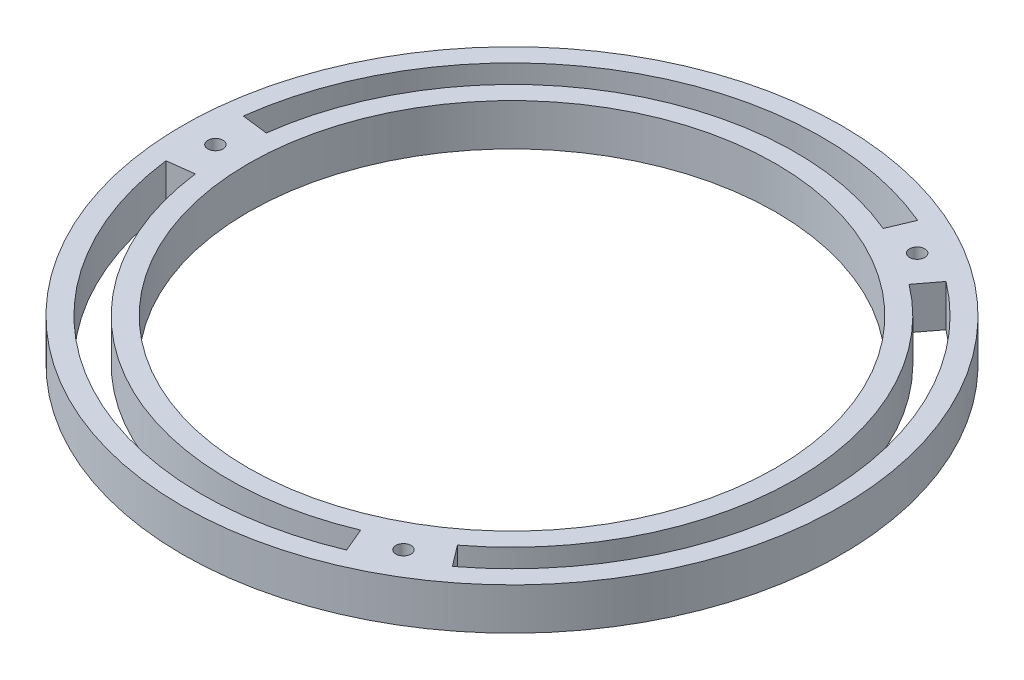
SolidWorks part; units mm, degrees
ref_plane "Front Plane" through (0, 0, 0) normal (0, 0, 1) x (1, 0, 0)
ref_plane "Top Plane" through (0, 0, 0) normal (0, 1, 0) x (1, 0, 0)
ref_plane "Right Plane" through (0, 0, 0) normal (1, 0, 0) x (0, 0, -1)
sketch "Sketch1" plane through (0, 0, 0) normal (0, 1, 0) x (1, 0, 0)
  line L0 (-50, 0) -> (50, 0) construction
  line L1 (-25, 43.3013) -> (25, -43.3013) construction
  line L2 (-25, -43.3013) -> (25, 43.3013) construction
  line L3 (30.2166, 39.8366) -> (24.1733, 31.8693)
  line L4 (19.3913, 46.0866) -> (15.513, 36.8693)
  line L5 (30.2166, -39.8366) -> (24.1733, -31.8693)
  line L6 (19.3913, -46.0866) -> (15.513, -36.8693)
  line L7 (-49.6078, 6.25) -> (-39.6863, 5)
  line L8 (-49.6078, -6.25) -> (-39.6863, -5)
  line L9 (0, 0) -> (15.513, 36.8693) construction
  line L10 (0, 0) -> (24.1733, 31.8693) construction
  line L11 (0, 0) -> (24.1733, -31.8693) construction
  line L12 (0, 0) -> (15.513, -36.8693) construction
  line L13 (0, 0) -> (-39.6863, 5) construction
  line L14 (-39.6863, -5) -> (0, 0) construction
  circle A0 centre (0, 0) radius 50
  circle A1 centre (0, 0) radius 47
  circle A2 centre (0, 0) radius 43
  circle A3 centre (0, 0) radius 40
  point P10 (0, 0)
  point P14 (0, 0)
  point P17 (0, 0)
  dimension "D1" = 100
  dimension "D2" = 3
  dimension "D5" = 60
  dimension "D6" = 60
  dimension "D7" = 5
  dimension "D8" = 5
  dimension "D9" = 5
  dimension "D10" = 5
  dimension "D11" = 5
  dimension "D12" = 5
  dimension "D3" = 4
  dimension "D4" = 3
extrude "Boss-Extrude1" add sketch "Sketch1" along normal blind 6.35 contours A1 L5 A0 L3 | A3 L5 A2 L3 | A3 L6 A2 L5 | A2 L6 A1 L5 | A1 L6 A0 L5 | A1 L8 A0 L6 | A3 L8 A2 L6 | A3 L7 A2 L8 | A2 L7 A1 L8 | A1 L7 A0 L8 | A1 L4 A0 L7 | A3 L4 A2 L7 | A3 L3 A2 L4 | A2 L3 A1 L4 | A1 L3 A0 L4 region at (44.0425, 0, -21.8721) region at (24.1943, 0, -41.9057) region at (22.4559, 0, -38.8948) region at (18.0546, 0, -45.0217) region at (37.876, 0, -18.8097) region at (20.7047, 0, -35.8617) region at (24.1943, 0, 41.9057) region at (-48.3886, 0, 0) region at (15.4453, 0, -38.5252) region at (22.4559, 0, 38.8948) region at (-44.9118, 0, 0) region at (-24.5905, 0, 42.592) region at (20.7047, 0, 35.8617) region at (-41.4095, 0, 0) region at (-21.1477, 0, 36.6289)
sketch "Sketch2" plane through (0, 6.35, 0) normal (0, 1, 0) x (1, 0, 0)
  line L1 (25, 43.3013) -> (20, 34.641) construction
  line L2 (20, -34.641) -> (25, -43.3013) construction
  line L3 (0, 0) -> (25.9863, -34.2595) construction
  line L4 (0, 0) -> (-40, 0) construction
  line L6 (0, 0) -> (20, -34.641) construction
  line L7 (-40, 0) -> (-50, 0) construction
  line L8 (0, 0) -> (20, 34.641) construction
  line L9 (0, 0) -> (16.6765, 39.6345) construction
  circle A0 centre (-45, 0) radius 1.15
  circle A1 centre (22.5, -38.9711) radius 1.15
  circle A2 centre (22.5, 38.9711) radius 1.15
  circle A3 centre (0, 0) radius 40 construction
  circle A4 centre (0, 0) radius 50 construction
  dimension "D1" = 2.3
  dimension "D2" = 5
  dimension "D3" = 5
extrude "M2 holes" cut sketch "Sketch2" against normal up to next
